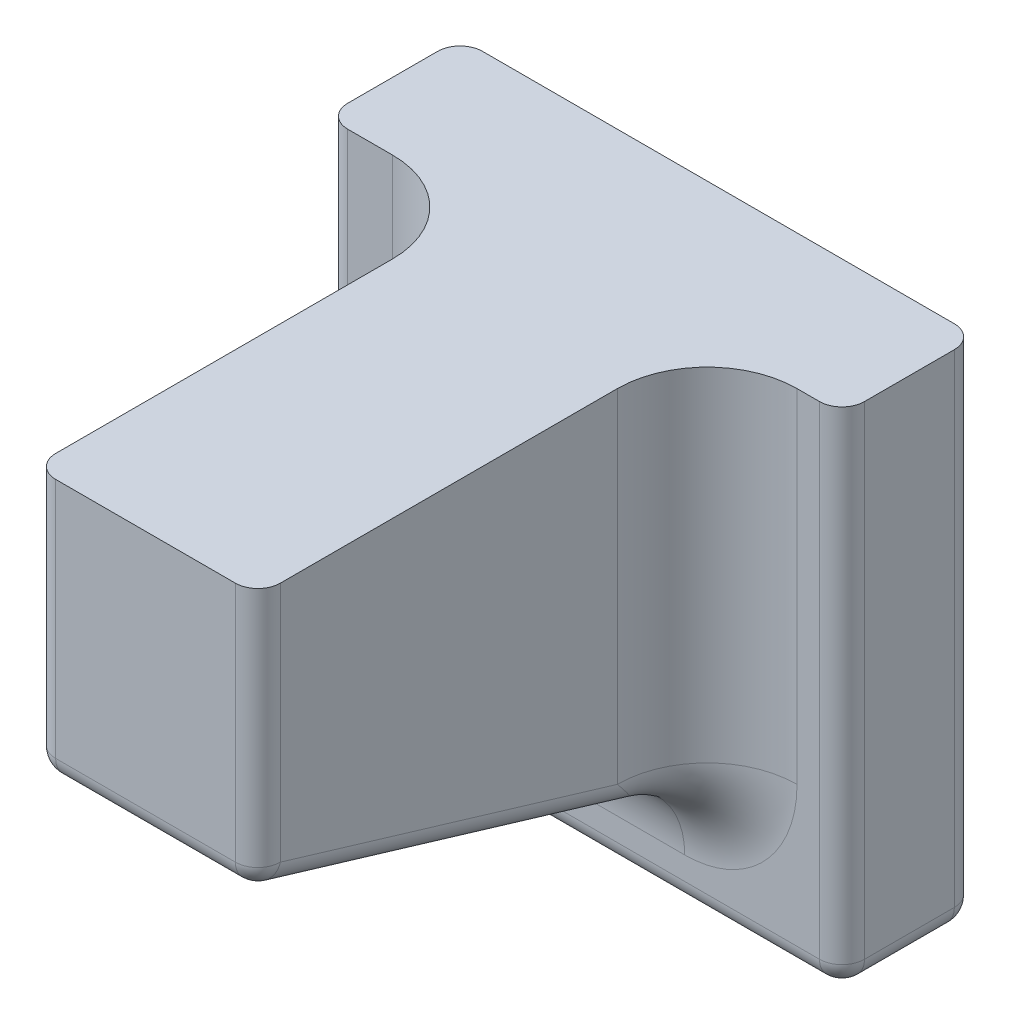
SolidWorks part; units mm, degrees
ref_plane "Front Plane" through (0, 0, 0) normal (0, 0, 1) x (1, 0, 0)
ref_plane "Top Plane" through (0, 0, 0) normal (0, 1, 0) x (1, 0, 0)
ref_plane "Right Plane" through (0, 0, 0) normal (1, 0, 0) x (0, 0, -1)
sketch "Sketch1" plane through (0, 0, 0) normal (0, 1, 0) x (1, 0, 0)
  line L0 (-11.5, 0) -> (0, 0)
  line L1 (0, 0) -> (11.5, 0)
  line L2 (11.5, 0) -> (11.5, 6)
  line L3 (11.5, 6) -> (6.05, 6)
  line L4 (6.05, 6) -> (7.75, 3.2)
  line L5 (7.75, 3.2) -> (-7.75, 3.2)
  line L6 (0, 0) -> (0, 3.2) construction
  line L7 (-11.5, 0) -> (-11.5, 6)
  line L8 (-6.05, 6) -> (-7.75, 3.2)
  line L9 (-11.5, 6) -> (-6.05, 6)
  point P3 (-7.75, 6.6736)
  point P12 (-4.9514, 15.5)
  dimension "D1" = 15.5
  dimension "D2" = 2.8
  dimension "D3" = 1.7
  dimension "D4" = 6
  dimension "D5" = 23
extrude "Boss-Extrude1" add sketch "Sketch1" along normal blind 20
sketch "Sketch2" plane through (0, 0, 0) normal (0, 0, 1) x (1, 0, 0)
  line L0 (-11.5, 0) -> (11.5, 0) construction
  line L1 (-4.5, 0) -> (4.5, 0)
  line L2 (-4.5, 0) -> (-4.5, 20)
  line L3 (-4.5, 20) -> (4.5, 20)
  line L4 (4.5, 0) -> (4.5, 20)
  line L5 (-4.5, 0) -> (4.5, 20) construction
  line L6 (-4.5, 20) -> (4.5, 0) construction
  line L7 (-11.5, 20) -> (11.5, 20) construction
  line L8 (0, 0) -> (0, 10) construction
  line L10 (4.5, 20) -> (5.5, 20)
  line L11 (4.5, 20) -> (4.5, 0)
  line L12 (4.5, 0) -> (5.5, 0)
  line L13 (5.5, 20) -> (5.5, 0)
  line L14 (4.5, 20) -> (5.5, 0) construction
  line L15 (4.5, 0) -> (5.5, 20) construction
  point P4 (0, 10)
  point P14 (5, 10)
  line M6 (-11.5, 0) -> (11.5, 0)
  line M8 (11.5, 20) -> (-11.5, 20)
  dimension "D1" = 9
  dimension "D2" = 1
extrude "Boss-Extrude2" add sketch "Sketch2" along normal blind 20 contours L4 L2 M6 M8 | L13 L4 M8 M6 region at (0, 10, 0) region at (5, 10, 0)
sketch "Sketch3" plane through (0, 20, 0) normal (0, 1, 0) x (1, 0, 0)
  line L0 (-6.05, 6) -> (6.05, 6)
  line L12 (-11.5, 6) -> (-11.5, 0)
  line L13 (-11.5, 0) -> (-4.5, 0)
  line L15 (-4.5, 0) -> (-4.5, -20)
  line L16 (-4.5, 0) -> (-4.5, -20)
  line L17 (5.5, 0) -> (11.5, 0)
  line L18 (11.5, 0) -> (11.5, 6)
  line L19 (11.5, 6) -> (6.05, 6)
  line L20 (6.05, 6) -> (7.75, 3.2)
  line L21 (7.75, 3.2) -> (-7.75, 3.2)
  line L22 (-7.75, 3.2) -> (-6.05, 6)
  line L23 (-6.05, 6) -> (-11.5, 6)
  line L24 (-11.5, 6) -> (-11.5, 0)
  line L25 (-11.5, 0) -> (-4.5, 0)
  line L30 (11.5, 0) -> (11.5, 6)
  line L31 (11.5, 6) -> (6.05, 6)
  line L35 (-6.05, 6) -> (-11.5, 6)
  line L36 (5.5, 0) -> (11.5, 0)
  line L37 (-4.5, -20) -> (5.5, -20)
  line L38 (-4.5, -20) -> (5.5, -20)
  line L39 (5.5, -20) -> (5.5, 0)
  line L40 (5.5, -20) -> (5.5, 0)
  dimension "D1" = 0
extrude "Boss-Extrude3" add sketch "Sketch3" along normal blind 2.5
fillet "Fillet1" radius 1 7 edges at (0, 0, -3.2) (11.5, 11.25, -6) (11.5, 11.25, 0) (-11.5, 11.25, 0) (-11.5, 11.25, -6) (5.5, 11.25, 20) (-4.5, 11.25, 20)
sketch "Sketch4" plane through (5.5, 0, 0) normal (1, 0, 0) x (0, 0, -1)
  line L0 (-20, 11) -> (0, 5)
  line L1 (-20, 0) -> (-20, 22.5) construction
  line L3 (-20, 11) -> (-20, 0)
  line L4 (-20, 0) -> (0, 0)
  line L5 (0, 0) -> (0, 5)
  line L6 (0, 22.5) -> (0, 0) construction
  point P4 (0.0238, 1.7208)
  point P5 (0, 0)
  point P11 (0, 4.7038)
  point P12 (0, 0)
  dimension "D1" = 5
  dimension "D2" = 11
extrude "Cut-Extrude1" cut sketch "Sketch4" against normal through all both and the other way through all
fillet "Fillet2" radius 1 16 edges at (5.5, 7.85, 9.5) (5.2071, 10.9121, 19.7071) (0.5, 11, 20) (-4.2071, 10.9121, 19.7071) (11.2071, 0, -0.2929) (11.5, 0, -3) (11.2071, 0, -5.7071) (8.275, 0, -6) (7.2036, 0, -4.1) (-7.2036, 0, -4.1) (-8.275, 0, -6) (-11.2071, 0, -5.7071) (-11.5, 0, -3) (-11.2071, 0, -0.2929) (0, 0, 0) (-4.5, 7.85, 9.5)
fillet "Fillet3" radius 4 5 edges at (0.5, 5, 0) (-4.5, 14.272, 0) (-4.2071, 5.3058, 0) (5.5, 14.272, 0) (5.2071, 5.3058, 0)
